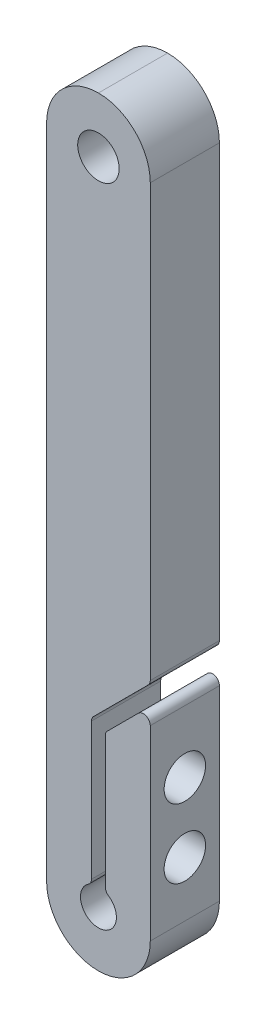
SolidWorks part; units mm, degrees
ref_plane "Front" through (0, 0, 0) normal (0, 0, 1) x (1, 0, 0)
ref_plane "Top" through (0, 0, 0) normal (0, 1, 0) x (1, 0, 0)
ref_plane "Right" through (0, 0, 0) normal (1, 0, 0) x (0, 0, -1)
sketch "Esquisse1" plane through (0, 0, 0) normal (0, 0, 1) x (1, 0, 0)
  line L1 (0, 0) -> (15, 0)
  line L2 (0, 0) -> (0, 110)
  line L3 (0, 110) -> (15, 110)
  line L4 (15, 0) -> (15, 110)
  dimension "D1" = 15
  dimension "D2" = 110
extrude "Boss.-Extru.1" add sketch "Esquisse1" along normal blind 10
sketch "Esquisse2" plane through (0, 0, 10) normal (0, 0, 1) x (1, 0, 0)
  line L0 (7.5, 110) -> (7.5, 81) construction
  line L1 (15, 110) -> (0, 110) construction
  line L2 (0, 0) -> (15, 0) construction
  line L3 (7.5, 8) -> (7.5, 0) construction
  circle A1 centre (7.5, 102) radius 3
  circle A2 centre (7.5, 8) radius 2.6
  point P11 (7.5, 0)
  dimension "D2" = 8
  dimension "D3" = 6
  dimension "D4" = 5.2
  dimension "D5" = 8
extrude "Enlèv. mat.-Extru.1" cut sketch "Esquisse2" against normal up to vertex (10 mm away) up to point (0, 110, 0)
fillet "Congé1" radius 7.5 4 edges at (15, 110, 5) (0, 110, 5) (15, 0, 5) (0, 0, 5)
sketch "Esquisse3" plane through (0, 0, 10) normal (0, 0, 1) x (1, 0, 0)
  line L0 (6.5, 10.4) -> (6.5, 31.2284)
  line L1 (6.5, 31.2284) -> (15, 39.7284)
  line L2 (15, 7.5) -> (15, 102.5) construction
  line L3 (15, 39.7284) -> (15, 36.9)
  line L4 (15, 36.9) -> (8.5, 30.4)
  line L5 (8.5, 30.4) -> (8.5, 10.4)
  line L6 (8.5, 10.4) -> (6.5, 10.4)
  line L7 (7.5, 10.6) -> (7.5, 10.4) construction
  circle A0 centre (7.5, 8) radius 2.6 construction
  point P10 (8.5865, 9.3621)
  dimension "D1" = 2
  dimension "D2" = 2
  dimension "D3" = 20
  dimension "D4" = 135
extrude "Enlèv. mat.-Extru.2" cut sketch "Esquisse3" against normal through all
sketch "Esquisse4" plane through (15, 0, 0) normal (1, 0, 0) x (0, 0, -1)
  line L0 (-5, 7.5) -> (-5, 36.9) construction
  line L1 (-10, 7.5) -> (0, 7.5) construction
  line L2 (0, 36.9) -> (-10, 36.9) construction
  circle A0 centre (-5, 15.5) radius 2.1
  circle A1 centre (-5, 25.5) radius 2.1
  dimension "D1" = 10
  dimension "D2" = 4.2
  dimension "D3" = 8
extrude "Enlèv. mat.-Extru.3" cut sketch "Esquisse4" against normal through all
sketch "Esquisse5" plane through (15, 0, 0) normal (1, 0, 0) x (0, 0, -1)
  circle A0 centre (-5, 25.5) radius 3
  circle A1 centre (-5, 15.5) radius 3
  dimension "D1" = 6
extrude "Enlèv. mat.-Extru.4" cut sketch "Esquisse5" against normal up to vertex (6.5 mm away) up to point (8.5, 30.4, 0)
fillet "Congé2" radius 1 6 edges at (15, 36.9, 5) (8.5, 10.4, 5) (6.5, 10.4, 5) (8.5, 30.4, 5) (15, 39.7284, 5) (6.5, 31.2284, 5)
